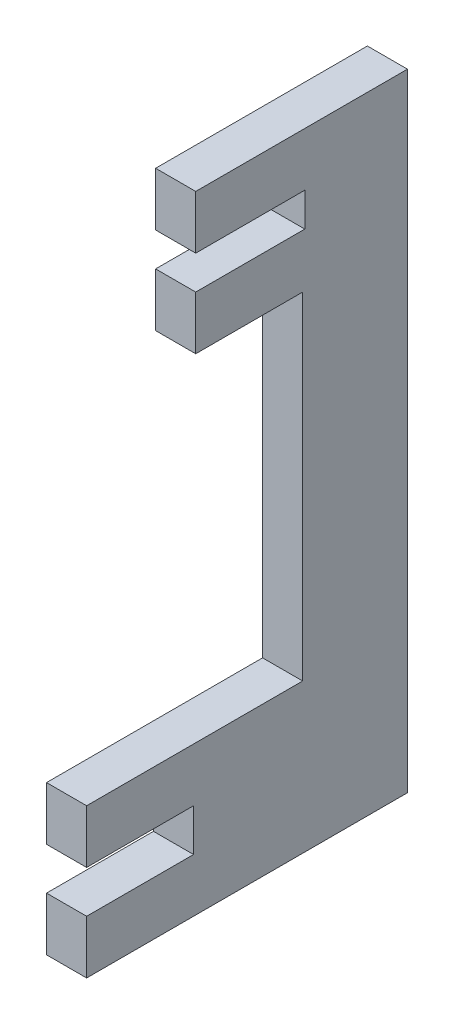
SolidWorks part; units mm, degrees
material "Corrugated Paper"
ref_plane "Front Plane" through (0, 0, 0) normal (0, 0, 1) x (1, 0, 0)
ref_plane "Top Plane" through (0, 0, 0) normal (0, 1, 0) x (1, 0, 0)
ref_plane "Right Plane" through (0, 0, 0) normal (1, 0, 0) x (0, 0, -1)
sketch "Sketch1" plane through (0, 0, 0) normal (1, 0, 0) x (0, 0, -1)
  line L0 (-12.7, -2.5082) -> (-12.7, -8.8582)
  line L1 (-12.7, 2.5082) -> (0, 2.5082)
  line L3 (-12.7, -2.5082) -> (0, -2.5082)
  line L4 (0, 2.5082) -> (0, -2.5082)
  line L5 (-12.7, -8.8582) -> (25.4, -8.8582)
  line L6 (-12.7, 2.5082) -> (-12.7, 8.8582)
  line L7 (-12.7, 8.8582) -> (12.954, 8.8582)
  line L8 (25.4, -8.8582) -> (25.4, 65.5583)
  line L9 (12.954, 8.8582) -> (12.954, 48.8582)
  line L10 (12.954, 48.8582) -> (0.254, 48.8582)
  line L11 (25.4, 65.5583) -> (0.254, 65.5583)
  line L12 (0.254, 65.5583) -> (0.254, 59.2082)
  line L13 (0.254, 59.2082) -> (13.208, 59.2082)
  line L14 (13.208, 59.2082) -> (13.208, 55.2082)
  line L15 (13.208, 55.2082) -> (0.254, 55.2082)
  line L16 (0.254, 55.2082) -> (0.254, 48.8582)
  line L17 (12.954, 59.2082) -> (12.954, 55.2082) construction
  dimension "D1" = 5.0165
  dimension "D2" = 12.7
  dimension "D3" = 25.4
  dimension "D4" = 6.35
  dimension "D5" = 6.35
  dimension "D6" = 12.954
  dimension "D7" = 40
  dimension "D8" = 4
  dimension "D9" = 12.7
  dimension "D10" = 6.35
  dimension "D11" = 0.254
extrude "Boss-Extrude1" add sketch "Sketch1" along normal blind 4.7625
equation "\"rodThick\"= 3/16in"
equation "\"thick\"= 3/16in"
equation "\"clear\"= 0.01in"
equation "\"D1@Sketch1\"=\"thick\"+\"clear\""
equation "\"D6@Sketch1\"= 0.5 + \"clear\""
equation "\"D1@Boss-Extrude1\"=\"thick\""
equation "\"D11@Sketch1\"=\"clear\""
